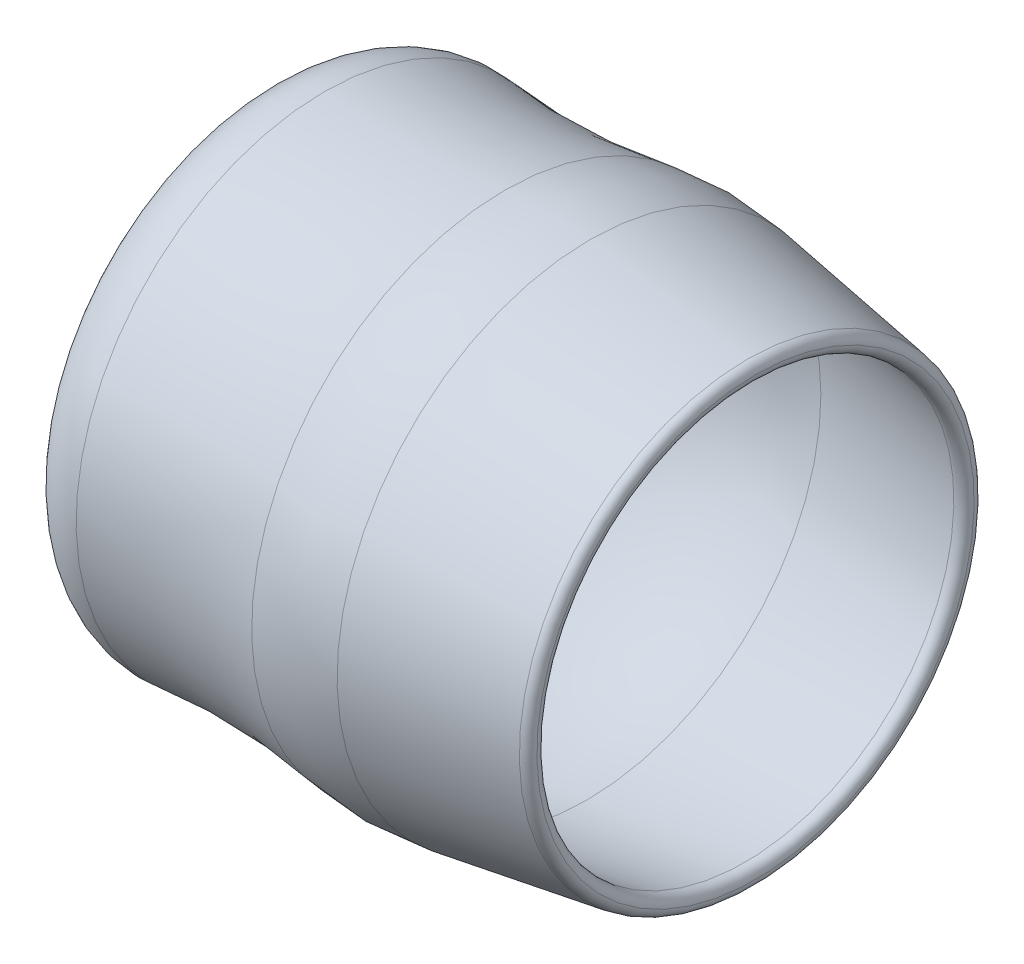
SolidWorks part; units mm, degrees
material "BUTYL"
ref_plane "Front Plane" through (0, 0, 0) normal (0, 0, 1) x (1, 0, 0)
ref_plane "Top Plane" through (0, 0, 0) normal (0, 1, 0) x (1, 0, 0)
ref_plane "Right Plane" through (0, 0, 0) normal (1, 0, 0) x (0, 0, -1)
sketch "Sketch1" plane through (0, 0, 0) normal (0, 0, 1) x (1, 0, 0)
  line L0 (66.3989, -5.6497) -> (-73.6011, -5.6497) construction
  line L1 (66.3989, -0.6497) -> (-73.6011, -0.6497) construction
  line L2 (66.3989, -10.6497) -> (-73.6011, -10.6497) construction
  line L3 (-3.6011, 2.7918) -> (-3.6011, -14.0897) construction
  line L4 (86.3989, -5.6497) -> (-86.1011, -5.6497) construction
  line L5 (-62.6011, 6.2858) -> (-62.6011, -17.5853) construction
  line L6 (-88.1011, 7.8503) -> (-88.1011, -19.1497) construction
  line L7 (-86.1011, -5.6497) -> (-88.1011, -5.6497) construction
  arc A3 (-71.4788, 6.6688) -> (-86.1011, -5.6497) centre (-73.6011, -5.6497) ccw construction
  arc A4 (86.3989, -5.6497) -> (60.965, 13.5979) centre (66.3989, -5.6497) ccw construction
  arc A5 (-71.4788, 6.6688) -> (60.965, 13.5979) centre (-20.5431, 302.3131) ccw construction
  arc A6 (-71.4788, 6.6688) -> (-71.4788, -17.9682) centre (-73.6011, -5.6497) ccw construction
  arc A7 (-71.4788, -17.9682) -> (60.965, -24.8974) centre (-20.5431, -313.6125) cw construction
  arc A8 (-71.309, 7.6543) -> (-62.6011, 6.2858) centre (-20.5431, 302.3131) ccw construction
  arc A9 (-71.309, 7.6543) -> (-87.1011, -5.6497) centre (-73.6011, -5.6497) ccw construction
  arc A10 (-71.309, 7.6543) -> (-71.309, -18.9537) centre (-73.6011, -5.6497) ccw construction
  arc A11 (-71.309, -18.9537) -> (-62.6011, -17.5853) centre (-20.5431, -313.6125) cw construction
  arc A12 (-88.5694, 4.8426) -> (-88.1011, -19.1497) centre (-11.2783, -5.6497) ccw construction
  arc A13 (-71.309, 7.6543) -> (60.6933, 14.5603) centre (-20.5431, 302.3131) ccw construction
  arc A14 (-71.309, -18.9537) -> (60.6933, -25.8598) centre (-20.5431, -313.6125) cw construction
  arc A15 (-75.7847, 7.6725) -> (-85.2689, 7.4211) centre (-81.4457, 42.2117) cw construction
  arc A16 (-88.5694, 4.8426) -> (-85.2689, 7.4211) centre (-85.5966, 4.4391) cw construction
  point P41 (0, 0)
  dimension "D1" = 140
  dimension "D2" = 25
  dimension "D3" = 40
  dimension "D4" = 300
  dimension "D18" = 78
  dimension "D19" = 35
  dimension "D20" = 3
  dimension "D5" = 70
  dimension "D6" = 8.44
  dimension "D7" = 60.965
  dimension "D8" = 6.6688
  dimension "D9" = 1
  dimension "D10" = 1
  dimension "D11" = 0.6497
  dimension "D12" = 1
  dimension "D13" = 10.6497
  dimension "D15" = 11
  dimension "D16" = 27
  dimension "D17" = 2
  dimension "D14" = 1
sketch "Sketch2" plane through (0, 0, 0) normal (0, 0, 1) x (1, 0, 0)
  line L0 (-86.1011, -5.6497) -> (-88.1011, -5.6497) construction
  line L1 (-62.6011, 6.2858) -> (-62.6011, -17.5853) construction
  line L2 (86.3989, -5.6497) -> (-86.1011, -5.6497) construction
  line L3 (-86.1011, -5.6497) -> (-88.1011, -5.6497)
  line L4 (-62.6011, 6.2858) -> (-62.6011, 5.2758)
  line L5 (86.3989, -5.6497) -> (-86.1011, -5.6497) construction
  line L6 (-88.1011, -5.6497) -> (-89.2783, -5.6497)
  arc A0 (-71.4788, 6.6688) -> (-86.1011, -5.6497) centre (-73.6011, -5.6497) ccw construction
  arc A1 (-71.4788, 6.6688) -> (60.965, 13.5979) centre (-20.5431, 302.3131) ccw construction
  arc A2 (-71.309, 7.6543) -> (-62.6011, 6.2858) centre (-20.5431, 302.3131) ccw construction
  arc A3 (-71.309, 7.6543) -> (-87.1011, -5.6497) centre (-73.6011, -5.6497) ccw construction
  arc A4 (-88.5694, 4.8426) -> (-88.1011, -19.1497) centre (-11.2783, -5.6497) ccw construction
  arc A5 (-85.2689, 7.4211) -> (-88.5694, 4.8426) centre (-85.5966, 4.4391) ccw construction
  arc A6 (-85.2689, 7.4211) -> (-75.7847, 7.6725) centre (-81.4457, 42.2117) ccw construction
  arc A7 (-71.4788, 6.6688) -> (-86.1011, -5.6497) centre (-73.6011, -5.6497) ccw
  arc A8 (-71.4788, 6.6688) -> (-62.6011, 5.2758) centre (-20.5431, 302.3131) ccw
  arc A9 (-71.309, 7.6543) -> (-62.6011, 6.2858) centre (-20.5431, 302.3131) ccw
  arc A10 (-71.309, 7.6543) -> (-75.7847, 7.6725) centre (-73.6011, -5.6497) ccw
  arc A11 (-88.5694, 4.8426) -> (-89.2783, -5.6497) centre (-11.2783, -5.6497) ccw
  arc A12 (-85.2689, 7.4211) -> (-88.5694, 4.8426) centre (-85.5966, 4.4391) ccw
  arc A13 (-85.2689, 7.4211) -> (-75.7847, 7.6725) centre (-81.4457, 42.2117) ccw
revolve "Revolve1" add sketch "Sketch2" angle 360 about L5
fillet "Fillet1" radius 0.5 2 edges at (-62.6011, 5.2758, 0) (-62.6011, 6.2858, 0)
ref_plane "Plane1" through (-73.6011, 0, 0) normal (1, 0, 0) x (0, 0, -1)
sketch "Sketch3" plane through (-73.6011, 0, 0) normal (1, 0, 0) x (0, 0, -1)
  circle A0 centre (0, -5.6497) radius 12.5
  dimension "D1" = 25
